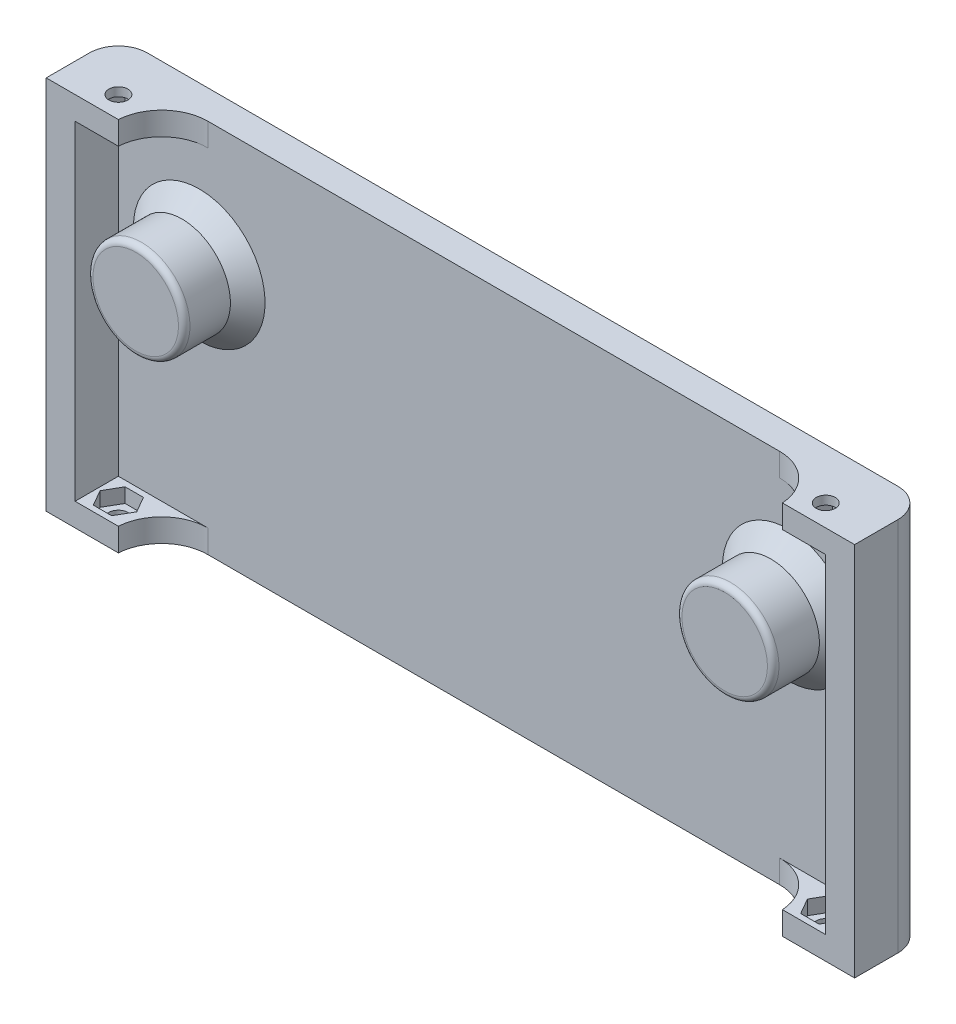
SolidWorks part; units mm, degrees
ref_plane "Front Plane" through (0, 0, 0) normal (0, 0, 1) x (1, 0, 0)
ref_plane "Top Plane" through (0, 0, 0) normal (0, 1, 0) x (1, 0, 0)
ref_plane "Right Plane" through (0, 0, 0) normal (1, 0, 0) x (0, 0, -1)
sketch "Sketch1" plane through (0, 0, 0) normal (0, 0, 1) x (1, 0, 0)
  line L1 (0, 0) -> (140, 0)
  line L2 (0, 0) -> (0, 65)
  line L3 (0, 65) -> (140, 65)
  line L4 (140, 0) -> (140, 65)
  dimension "D1" = 65
  dimension "D2" = 140
extrude "Boss-Extrude1" add sketch "Sketch1" along normal blind 12.5
sketch "Sketch3" plane through (0, 65, 0) normal (0, 1, 0) x (1, 0, 0)
  line L0 (5, -12.5) -> (135, -12.5)
  line L9 (135, -5) -> (135, -12.5)
  line L10 (5, -5) -> (135, -5)
  line L11 (5, -12.5) -> (5, -5)
  line L12 (135, -5) -> (135, -12.5)
  line L13 (5, -5) -> (135, -5)
  line L14 (5, -12.5) -> (5, -5)
  dimension "D1" = 5
extrude "Cut-Extrude1" cut sketch "Sketch3" against normal through all
fillet "Fillet1" radius 5 2 edges at (140, 32.5, 0) (0, 32.5, 0)
sketch "Sketch4" plane through (0, 0, 0) normal (0, -1, 0) x (1, 0, 0)
  line L0 (135, 5) -> (5, 5) construction
  line L1 (5, 12.5) -> (12.5, 12.5)
  line L2 (5, 12.5) -> (5, 5)
  line L3 (5, 5) -> (12.5, 5)
  line L4 (12.5, 12.5) -> (12.5, 5)
  line L6 (135, 5) -> (127.5, 5)
  line L7 (135, 5) -> (135, 12.5)
  line L8 (135, 12.5) -> (127.5, 12.5)
  line L9 (127.5, 5) -> (127.5, 12.5)
  point P12 (135, 12.5)
extrude "Boss-Extrude2" add sketch "Sketch4" against normal blind 4
sketch "Sketch5" plane through (0, 4, 0) normal (0, 1, 0) x (1, 0, 0)
  line L0 (131.25, -5) -> (131.25, -12.5) construction
  line L1 (127.5, -5) -> (135, -5) construction
  line L2 (135, -12.5) -> (127.5, -12.5) construction
  line L3 (70, 0) -> (70, -12.5) construction
  line L4 (134.4254, -8.75) -> (132.8377, -6)
  line L5 (132.8377, -6) -> (129.6623, -6)
  line L6 (129.6623, -6) -> (128.0746, -8.75)
  line L7 (128.0746, -8.75) -> (129.6623, -11.5)
  line L8 (129.6623, -11.5) -> (132.8377, -11.5)
  line L9 (132.8377, -11.5) -> (134.4254, -8.75)
  line L10 (135, 0) -> (5, 0) construction
  line L11 (10.3377, -6) -> (11.9254, -8.75)
  line L12 (11.9254, -8.75) -> (10.3377, -11.5)
  line L13 (7.1623, -11.5) -> (5.5746, -8.75)
  line L14 (10.3377, -11.5) -> (7.1623, -11.5)
  line L15 (7.1623, -6) -> (10.3377, -6)
  line L16 (5.5746, -8.75) -> (7.1623, -6)
  circle A0 centre (131.25, -8.75) radius 2.75 construction
  circle A1 centre (131.25, -8.75) radius 1.65
  circle A2 centre (8.75, -8.75) radius 1.65
  point P27 (131.25, -8.75)
  dimension "D2" = 3.3
  dimension "D1" = 5.5
extrude "Cut-Extrude2" cut sketch "Sketch5" against normal blind 2.5
extrude "Cut-Extrude3" cut sketch "Sketch5<3>" against normal through all contours A2 | A1 region at (131.25, 4, 8.75) region at (8.75, 4, 8.75)
sketch "Sketch5<3>" plane through (0, 4, 0) normal (0, 1, 0) x (1, 0, 0) same geometry as "Sketch5"
fillet "Fillet2" radius 8 2 edges at (127.5, 2, 5) (12.5, 2, 5)
ref_plane "Plane1" through (0, 32.5, 0) normal (0, 1, 0) x (1, 0, 0)
mirror "Mirror1" about plane through (0, 32.5, 0) normal (0, 1, 0) of "Cut-Extrude3", "Cut-Extrude2", "Boss-Extrude2", "Fillet2"
sketch "Sketch7" plane through (0, 0, 5) normal (0, 0, 1) x (1, 0, 0)
  line L0 (140, 0) -> (121, 0) construction
  line L1 (119.5156, 0) -> (20.4844, 0) construction
  line L2 (121, 0) -> (121, 42.7) construction
  line L3 (70, 65) -> (70, 0) construction
  line L4 (119.5156, 65) -> (20.4844, 65) construction
  circle A0 centre (121, 42.7) radius 8.4
  circle A1 centre (19, 42.7) radius 8.4
  point P11 (70, 0)
  dimension "D3" = 16.8
  dimension "D1" = 19
  dimension "D2" = 42.7
extrude "Boss-Extrude3" add sketch "Sketch7" along normal blind 11
fillet "Fillet3" radius 1 2 edges at (129.4, 42.7, 16) (10.6, 42.7, 16)
chamfer "Chamfer1" distance 3 angle 45 2 edges at (112.6, 42.7, 5) (10.6, 42.7, 5)
